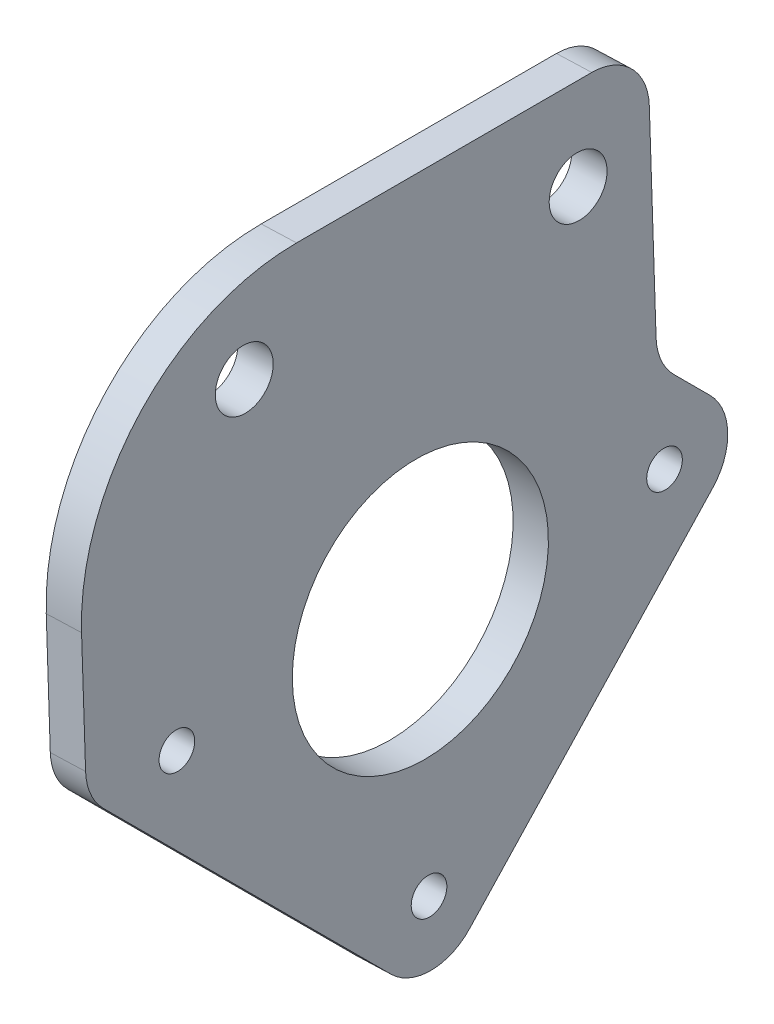
SolidWorks part; units mm, degrees
ref_plane "Front Plane" through (0, 0, 0) normal (0, 0, 1) x (1, 0, 0)
ref_plane "Top Plane" through (0, 0, 0) normal (0, 1, 0) x (1, 0, 0)
ref_plane "Right Plane" through (0, 0, 0) normal (1, 0, 0) x (0, 0, -1)
ref_plane "Plane1" through (158.6832, 5.4252, 0) normal (-0.9994, -0.0342, 0) x (0.0342, -0.9994, 0)
sketch "Sketch11" plane through (158.6832, 5.4252, 0) normal (-0.9994, -0.0342, 0) x (0.0342, -0.9994, 0)
  line L0 (-62.1562, 394.9262) -> (-62.1562, 368.3986)
  line L1 (-57.1562, 363.3986) -> (-39.3972, 363.3986)
  line L2 (-35.8617, 361.9341) -> (-32.7008, 358.7731)
  line L3 (-25.6297, 358.7731) -> (-3.0023, 381.4006)
  line L4 (-3.0023, 388.4716) -> (-27.9924, 413.4617)
  line L5 (-31.5279, 414.9262) -> (-42.1562, 414.9262)
  arc A0 (-62.1562, 368.3986) -> (-57.1562, 363.3986) centre (-57.1562, 368.3986) ccw
  arc A1 (-39.3972, 363.3986) -> (-35.8617, 361.9341) centre (-39.3972, 358.3986) cw
  arc A2 (-32.7008, 358.7731) -> (-25.6297, 358.7731) centre (-29.1652, 362.3087) ccw
  arc A3 (-3.0023, 381.4006) -> (-3.0023, 388.4716) centre (-6.5378, 384.9361) ccw
  arc A4 (-27.9924, 413.4617) -> (-31.5279, 414.9262) centre (-31.5279, 409.9262) ccw
  arc A5 (-42.1562, 414.9262) -> (-62.1562, 394.9262) centre (-42.1562, 394.9262) ccw
base flange "Base-Flange1" sketch "Sketch11" thickness 3.175 reverse thickness direction yes parameters "D1"=0
hole_wizard "Ø23.0 (23) Diameter Hole1" positions "Sketch17" profile "Sketch16" hole size "Ø23.0" standard "ANSI Metric"
sketch "Sketch17" plane through (158.6832, 5.4252, 0) normal (-0.9994, -0.0342, 0) x (0, 0, 1)
  point P0 (384.9262, 29.1916)
sketch "Sketch16" plane through (157.6857, 34.5998, 384.9262) normal (0, 0, 1) x (0.0342, -0.9994, 0)
  line L0 (0, 0) -> (0, 5.2451)
  line L1 (0, 5.2451) -> (11.5, 5.2451)
  line L2 (11.5, 5.2451) -> (11.5, 0)
  line L5 (11.5, 0) -> (0, 0)
  line L11 (0, -6.35) -> (0, 107.95) construction
  dimension "Thru Hole Dia." = 23
  dimension "Thru Hole Depth" = 5.2451
hole_wizard "Ø5.2 (5.2) Diameter Hole1" positions "Sketch19" profile "Sketch18" hole size "Ø5.2" standard "ANSI Metric"
sketch "Sketch19" plane through (158.6832, 5.4252, 0) normal (-0.9994, -0.0342, 0) x (0, 0, 1)
  point P0 (369.8986, 54.1562)
  point P1 (399.8986, 54.1562)
sketch "Sketch18" plane through (156.8327, 59.5498, 369.8986) normal (0, 0, 1) x (0.0342, -0.9994, 0)
  line L0 (0, 0) -> (0, 5.2451)
  line L1 (0, 5.2451) -> (2.6, 5.2451)
  line L2 (2.6, 5.2451) -> (2.6, 0)
  line L5 (2.6, 0) -> (0, 0)
  line L11 (0, -6.35) -> (0, 107.95) construction
  dimension "Thru Hole Dia." = 5.2
  dimension "Thru Hole Depth" = 5.2451
hole_wizard "Ø3.2 (3.2) Diameter Hole1" positions "Sketch21" profile "Sketch20" hole size "Ø3.2" standard "ANSI Metric"
sketch "Sketch21" plane through (158.6832, 5.4252, 0) normal (-0.9994, -0.0342, 0) x (0, 0, 1)
  point P0 (406.8061, 29.1277)
  point P1 (362.9911, 29.1277)
  point P2 (384.8986, 7.2202)
sketch "Sketch20" plane through (157.6879, 34.5359, 406.8061) normal (0, 0, 1) x (0.0342, -0.9994, 0)
  line L0 (0, 0) -> (0, 5.2451)
  line L1 (0, 5.2451) -> (1.6, 5.2451)
  line L2 (1.6, 5.2451) -> (1.6, 0)
  line L5 (1.6, 0) -> (0, 0)
  line L11 (0, -6.35) -> (0, 107.95) construction
  dimension "Thru Hole Dia." = 3.2
  dimension "Thru Hole Depth" = 5.2451
ref_point "Point5"
ref_point "Point4"
ref_point "Point1"
ref_plane "Plane3" through (-1.8505, 54.1246, 0) normal (-0.0342, 0.9994, 0) x (0.9994, 0.0342, 0)
sketch "Bend-Lines4" plane through (0, 0, 0) normal (0, 1, 0) x (1, 0, 0)
sketch "Bounding-Box4" plane through (0, 0, 0) normal (0, 1, 0) x (1, 0, 0)
sheet metal parameters "Sheet-Metal(5)" thickness 3.175 parameters "D1"=0
flat pattern "Flat-Pattern(5)" [suppressed]
sketch "Bend-Lines5" plane through (0, 0, 0) normal (0, 1, 0) x (1, 0, 0)
sketch "Bounding-Box5" [suppressed] plane through (0, 0, 0) normal (0, 1, 0) x (1, 0, 0)
sheet metal parameters "Sheet-Metal(6)" thickness 3.175 parameters "D1"=0
flat pattern "Flat-Pattern(5)"
sketch "Bend-Lines5" plane through (0, 0, 0) normal (0, 1, 0) x (1, 0, 0)
sketch "Bounding-Box5" [suppressed] plane through (0, 0, 0) normal (0, 1, 0) x (1, 0, 0)
sheet metal parameters "Sheet-Metal(7)" thickness 3.175 parameters "D1"=0
flat pattern "Flat-Pattern(5)"
sketch "Bend-Lines5" plane through (0, 0, 0) normal (0, 1, 0) x (1, 0, 0)
sketch "Bounding-Box5" [suppressed] plane through (0, 0, 0) normal (0, 1, 0) x (1, 0, 0)
sheet metal parameters "Sheet-Metal(8)" thickness 3.175 parameters "D1"=0
flat pattern "Flat-Pattern(5)"
sketch "Bend-Lines5" plane through (0, 0, 0) normal (0, 1, 0) x (1, 0, 0)
sketch "Bounding-Box5" [suppressed] plane through (0, 0, 0) normal (0, 1, 0) x (1, 0, 0)
